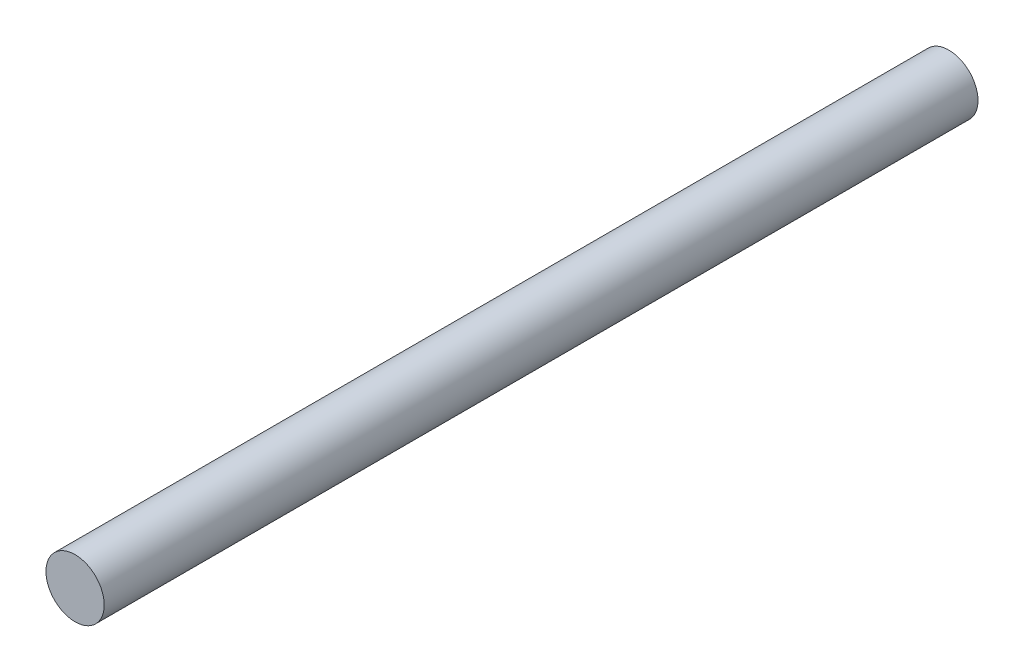
SolidWorks part; units mm, degrees
ref_plane "Front Plane" through (0, 0, 0) normal (0, 0, 1) x (1, 0, 0)
ref_plane "Top Plane" through (0, 0, 0) normal (0, 1, 0) x (1, 0, 0)
ref_plane "Right Plane" through (0, 0, 0) normal (1, 0, 0) x (0, 0, -1)
sketch "Sketch1" plane through (0, 0, 0) normal (0, 0, 1) x (1, 0, 0)
  circle A0 centre (0, 0) radius 4
  dimension "D1" = 8
extrude "Boss-Extrude1" add sketch "Sketch1" along normal mid plane 120
ref_axis "Axis" through (0, 0, 60) along (0, 0, -1)
